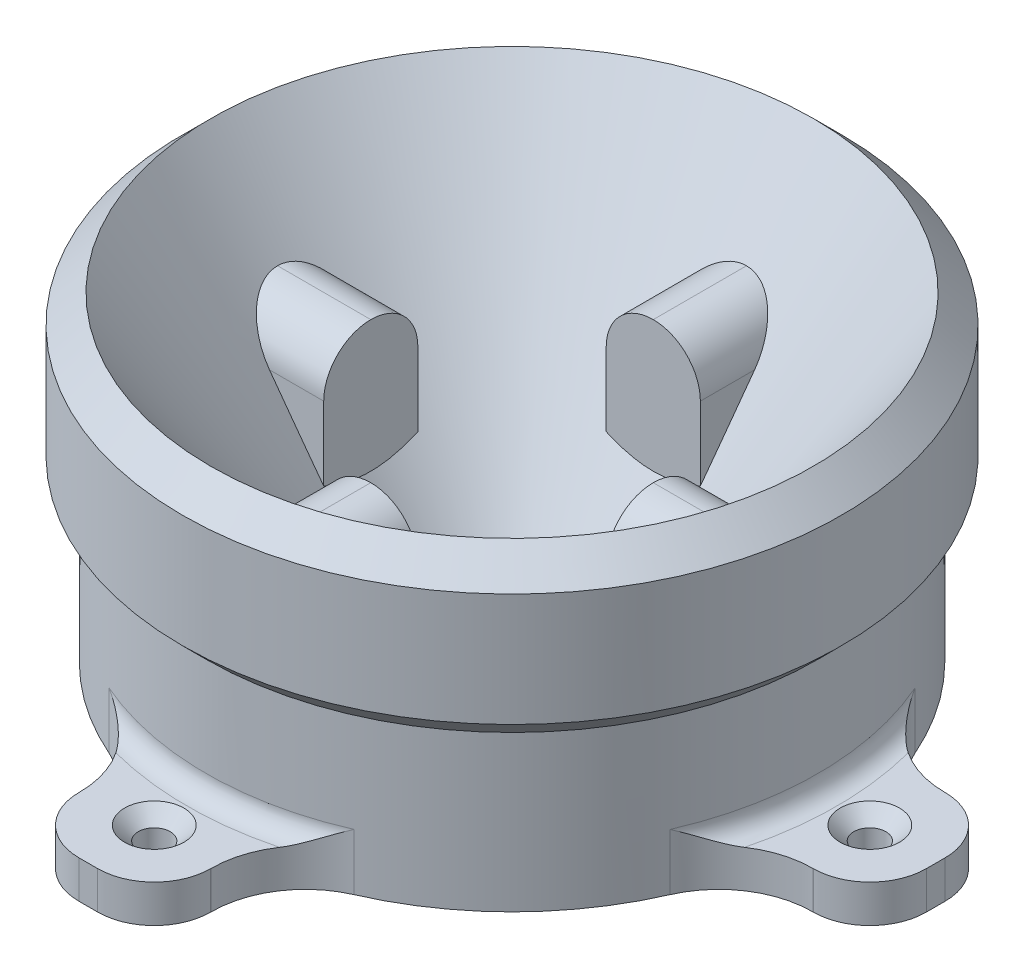
SolidWorks part; units mm, degrees
ref_plane "Front Plane" through (0, 0, 0) normal (0, 0, 1) x (1, 0, 0)
ref_plane "Top Plane" through (0, 0, 0) normal (0, 1, 0) x (1, 0, 0)
ref_plane "Right Plane" through (0, 0, 0) normal (1, 0, 0) x (0, 0, -1)
sketch "Sketch1" plane through (0, 0, 0) normal (0, 1, 0) x (1, 0, 0)
  line L0 (0, 0) -> (0, 60.437) construction
  line L1 (-1, 45) -> (1, 45)
  line L2 (-7, 39) -> (-7, 31.7372)
  line L3 (-1, -45) -> (1, -45)
  line L4 (7, 39) -> (7, 31.7372)
  line L5 (0, 0) -> (51.2532, 0) construction
  line L7 (-39, 7) -> (-31.7372, 7)
  line L8 (-45, 1) -> (-45, -1)
  line L9 (-39, -7) -> (-31.7372, -7)
  line L10 (45, 1) -> (45, -1)
  line L20 (7, -31.7372) -> (7, -39)
  line L21 (-7, -31.7372) -> (-7, -39)
  line L22 (31.7372, 7) -> (39, 7)
  line L23 (31.7372, -7) -> (39, -7)
  arc A0 (7, -31.7372) -> (31.7372, -7) centre (0, 0) ccw
  circle A1 centre (0, 0) radius 25
  arc A2 (-7, -39) -> (-1, -45) centre (-1, -39) ccw
  arc A3 (1, -45) -> (7, -39) centre (1, -39) ccw
  arc A4 (39, -7) -> (45, -1) centre (39, -1) ccw
  arc A5 (45, 1) -> (39, 7) centre (39, 1) ccw
  arc A6 (7, 39) -> (1, 45) centre (1, 39) ccw
  arc A7 (-1, 45) -> (-7, 39) centre (-1, 39) ccw
  arc A8 (-39, -7) -> (-45, -1) centre (-39, -1) cw
  arc A9 (-39, 7) -> (-45, 1) centre (-39, 1) ccw
  arc A10 (31.7372, 7) -> (7, 31.7372) centre (0, 0) ccw
  arc A11 (-31.7372, -7) -> (-7, -31.7372) centre (0, 0) ccw
  arc A12 (-7, 31.7372) -> (-31.7372, 7) centre (0, 0) ccw
  circle A17 centre (-38, 0) radius 1.6
  circle A18 centre (0, 38) radius 1.6
  circle A19 centre (0, -38) radius 1.6
  circle A20 centre (38, 0) radius 1.6
  dimension "D1" = 65
  dimension "D2" = 50
  dimension "D7" = 6
  dimension "D3" = 7
  dimension "D4" = 7
  dimension "D6" = 3.2
  dimension "D8" = 38
  dimension "D5" = 45
extrude "Boss-Extrude1" add sketch "Sketch1" along normal blind 4
fillet "Fillet1" radius 10 8 edges at (31.7372, 2, -7) (7, 2, -31.7372) (-7, 2, -31.7372) (-31.7372, 2, -7) (-31.7372, 2, 7) (-7, 2, 31.7372) (7, 2, 31.7372) (31.7372, 2, 7)
sketch "Sketch2" plane through (0, 4, 0) normal (0, 1, 0) x (1, 0, 0)
  circle A0 centre (0, 0) radius 32.5
  circle A1 centre (0, 0) radius 25
  dimension "D1" = 50
  dimension "D2" = 65
extrude "Boss-Extrude2" add sketch "Sketch2" along normal blind 10
sketch "Sketch3" plane through (0, 14, 0) normal (0, 1, 0) x (1, 0, 0)
  circle A1 centre (0, 0) radius 35
  circle A2 centre (0, 0) radius 25
  dimension "D1" = 70
  dimension "D2" = 50
extrude "Boss-Extrude3" add sketch "Sketch3" along normal blind 20
sketch "Sketch5" plane through (0, 0, 0) normal (0, 0, 1) x (1, 0, 0)
  line L1 (-25, 0) -> (25, 0) construction
  line L2 (35, 34) -> (-35, 34) construction
  line L3 (-25.0992, 34) -> (-25, 0)
  line L4 (-25, 0) -> (-10, 0)
  line L5 (0, 0) -> (0, 41.3664) construction
  line L6 (-10, 0) -> (-10, 34)
  line L7 (25, 34) -> (-25, 34) construction
  line L8 (-10, 34) -> (-25.0992, 34)
  dimension "D1" = 10
  dimension "D2" = 25
  dimension "D3" = 25.0992
revolve "Revolve1" add sketch "Sketch5" angle 360 about L5
sketch "Sketch6" plane through (0, 0, 0) normal (0, 0, 1) x (1, 0, 0)
  line L0 (0, 0) -> (0, 41.8244) construction
  line L4 (35, 34) -> (-35, 34) construction
  line L5 (-32, 34) -> (-10, 34)
  line L6 (10, 34) -> (-10, 34) construction
  line L7 (-10, 34) -> (-10, 3)
  line L8 (-32, 34) -> (-10, 3)
  line L9 (-29.7867, 0) -> (-13, 0) construction
  dimension "D1" = 32
  dimension "D2" = 3
  dimension "D3" = 10
revolve "Cut-Revolve1" cut sketch "Sketch6" angle 360 about L0
chamfer "Chamfer1" distance 5 angle 45 1 edges at (0, 14, 35)
ref_plane "Plane1" through (0, 24, 0) normal (0, 1, 0) x (1, 0, 0)
sketch "Sketch8" plane through (0, 24, 0) normal (0, 1, 0) x (1, 0, 0)
  line L0 (0, 0) -> (0, 55.3083) construction
  line L1 (-27.8028, 5) -> (-15, 5)
  line L2 (-27.8028, 5) -> (-27.8028, -5)
  line L3 (-27.8028, -5) -> (-15, -5)
  line L4 (-15, 5) -> (-15, -5)
  line L9 (5.001, 27.8038) -> (-4.999, 27.8038)
  line L10 (5.001, 27.8038) -> (5.001, 15.001)
  line L11 (5.001, 15.001) -> (-4.999, 15.001)
  line L12 (-4.999, 27.8038) -> (-4.999, 15.001)
  line L13 (27.8048, -5) -> (27.8048, 5)
  line L14 (27.8048, -5) -> (15.002, -5)
  line L15 (15.002, -5) -> (15.002, 5)
  line L16 (27.8048, 5) -> (15.002, 5)
  line L17 (-4.999, -27.8038) -> (5.001, -27.8038)
  line L18 (-4.999, -27.8038) -> (-4.999, -15.001)
  line L19 (-4.999, -15.001) -> (5.001, -15.001)
  line L20 (5.001, -27.8038) -> (5.001, -15.001)
  circle A0 centre (0, 0) radius 28.2489 construction
  circle A1 centre (0.001, 0.001) radius 28.2489 construction
  circle A2 centre (0.002, 0) radius 28.2489 construction
  circle A3 centre (0.001, -0.001) radius 28.2489 construction
  point P29 (0.001, 0)
  dimension "D2" = 56.4977
  dimension "D3" = 0.001
  dimension "D1" = 15
  dimension "D4" = 4
extrude "Boss-Extrude4" add sketch "Sketch8" against normal up to surface (12.8112 mm away) up to face at (0, 3, -10)
fillet "Fillet3" radius 5 8 edges at (-4.999, 24, 19.6987) (5.001, 24, 19.6985) (-19.6981, 24, -5) (-19.6981, 24, 5) (19.6991, 24, 5) (19.6991, 24, -5) (-4.999, 24, -19.6987) (5.001, 24, -19.6985)
fillet "Fillet4" radius 2 4 edges at (0, 4, -32.5) (32.5, 4, 0) (0, 4, 32.5) (-32.5, 4, 0)
hole_wizard "CSK for M3 Flat Head Machine Screw1" positions "Sketch9" profile "Sketch10" countersink size "M3" standard "ANSI Metric"
sketch "Sketch9" plane through (0, 4, 0) normal (0, 1, 0) x (1, 0, 0)
  point P0 (-38, 0)
  point P3 (0, 38)
  point P6 (38, 0)
  point P9 (0, -38)
sketch "Sketch10" plane through (-38, 4, 0) normal (1, 0, 0) x (0, 0, 1)
  line L0 (0, 0) -> (0, 41.0215)
  line L1 (0, 41.0215) -> (1.7, 40)
  line L2 (1.7, 40) -> (1.7, 1.45)
  line L3 (1.7, 1.45) -> (3.15, 0)
  line L5 (3.15, 0) -> (0, 0)
  line L6 (-1.7, 1.45) -> (-3.15, 0) construction
  line L10 (0, 41.0215) -> (-1.7, 40) construction
  line L11 (0, -6.35) -> (0, 107.95) construction
  dimension "Hole Dia." = 3.4
  dimension "Hole Depth" = 40
  dimension "Near C'Sink Dia." = 6.3
  dimension "Near C'Sink Angle" = 90
  dimension "Drill Angle" = 118
chamfer "Chamfer2" distance 3 angle 45 1 edges at (0, 34, 35)
